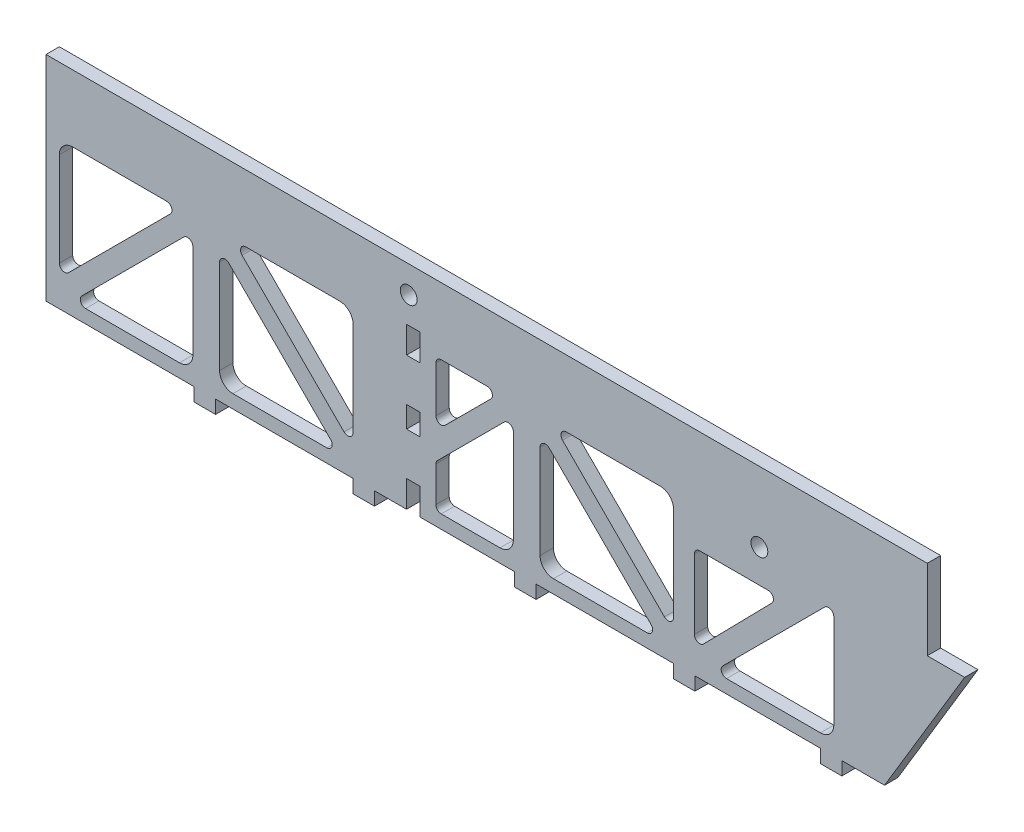
SolidWorks part; units mm, degrees
material "Pine"
ref_plane "Front Plane" through (0, 0, 0) normal (0, 0, 1) x (1, 0, 0)
ref_plane "Top Plane" through (0, 0, 0) normal (0, 1, 0) x (1, 0, 0)
ref_plane "Right Plane" through (0, 0, 0) normal (1, 0, 0) x (0, 0, -1)
sketch "Model" plane through (0, 0, 0) normal (0, 0, 1) x (1, 0, 0)
  line L0 (312.6855, 15.1239) -> (345.2281, 48.2988)
  line L1 (343.4149, 52.6175) -> (310.8722, 52.6175)
  line L2 (308.3322, 50.0775) -> (308.3322, 16.9026)
  line L8 (171.2321, 6.35) -> (215.9, 6.35)
  line L9 (217.9139, 59.1639) -> (169.4361, 10.6861)
  line L10 (222.25, 57.3679) -> (222.25, 12.7)
  line L11 (234.95, 57.3679) -> (234.95, 12.7)
  line L12 (239.2861, 59.1639) -> (287.7639, 10.6861)
  line L13 (241.3, 6.35) -> (285.9679, 6.35)
  line L14 (294.1139, 17.0361) -> (245.6361, 65.5139)
  line L15 (247.4321, 69.85) -> (292.1, 69.85)
  line L16 (298.45, 63.5) -> (298.45, 18.8321)
  line L17 (323.6321, 6.35) -> (368.3, 6.35)
  line L18 (370.3139, 59.1639) -> (321.8361, 10.6861)
  line L19 (374.65, 57.3679) -> (374.65, 12.7)
  line L20 (18.8321, 6.35) -> (63.5, 6.35)
  line L21 (17.0361, 10.6861) -> (65.5139, 59.1639)
  line L22 (69.85, 57.3679) -> (69.85, 12.7)
  line L23 (82.55, 57.3679) -> (82.55, 12.7)
  line L24 (86.8861, 59.1639) -> (135.3639, 10.6861)
  line L25 (88.9, 6.35) -> (133.5679, 6.35)
  line L26 (93.2361, 65.5139) -> (141.7139, 17.0361)
  line L27 (95.0321, 69.85) -> (139.7, 69.85)
  line L28 (146.05, 63.5) -> (146.05, 18.8321)
  line L29 (163.0861, 17.0361) -> (211.5639, 65.5139)
  line L30 (158.75, 63.5) -> (158.75, 18.8321)
  line L31 (165.1, 69.85) -> (209.7679, 69.85)
  line L35 (419.1, 87.376) -> (419.1, 71.374)
  line L36 (436.88, 87.376) -> (419.1, 87.376)
  line L37 (436.88, 87.376) -> (436.88, 95.25)
  line L38 (0, 95.25) -> (436.88, 95.25)
  line L39 (0, 0) -> (0, 95.25)
  line L40 (0, 0) -> (398.78, 0)
  line L41 (436.88, 63.5) -> (398.78, 0)
  line L42 (436.88, 63.5) -> (436.88, 71.374)
  line L43 (419.1, 71.374) -> (436.88, 71.374)
  line L44 (6.35, 63.5) -> (6.35, 18.8321)
  line L45 (12.7, 69.85) -> (57.3679, 69.85)
  line L46 (59.1639, 65.5139) -> (10.6861, 17.0361)
  arc A0 (215.9, 6.35) -> (222.25, 12.7) centre (215.9, 12.7) ccw
  arc A1 (169.4361, 10.6861) -> (171.2321, 6.35) centre (171.2321, 8.89) ccw
  arc A2 (222.25, 57.3679) -> (217.9139, 59.1639) centre (219.71, 57.3679) ccw
  arc A3 (239.2861, 59.1639) -> (234.95, 57.3679) centre (237.49, 57.3679) ccw
  arc A4 (285.9679, 6.35) -> (287.7639, 10.6861) centre (285.9679, 8.89) ccw
  arc A5 (234.95, 12.7) -> (241.3, 6.35) centre (241.3, 12.7) ccw
  arc A6 (247.4321, 69.85) -> (245.6361, 65.5139) centre (247.4321, 67.31) ccw
  arc A7 (298.45, 63.5) -> (292.1, 69.85) centre (292.1, 63.5) ccw
  arc A8 (294.1139, 17.0361) -> (298.45, 18.8321) centre (295.91, 18.8321) ccw
  arc A9 (321.8361, 10.6861) -> (323.6321, 6.35) centre (323.6321, 8.89) ccw
  arc A10 (374.65, 57.3679) -> (370.3139, 59.1639) centre (372.11, 57.3679) ccw
  arc A11 (368.3, 6.35) -> (374.65, 12.7) centre (368.3, 12.7) ccw
  arc A12 (63.5, 6.35) -> (69.85, 12.7) centre (63.5, 12.7) ccw
  arc A13 (17.0361, 10.6861) -> (18.8321, 6.35) centre (18.8321, 8.89) ccw
  arc A14 (69.85, 57.3679) -> (65.5139, 59.1639) centre (67.31, 57.3679) ccw
  arc A15 (86.8861, 59.1639) -> (82.55, 57.3679) centre (85.09, 57.3679) ccw
  arc A16 (133.5679, 6.35) -> (135.3639, 10.6861) centre (133.5679, 8.89) ccw
  arc A17 (82.55, 12.7) -> (88.9, 6.35) centre (88.9, 12.7) ccw
  arc A18 (95.0321, 69.85) -> (93.2361, 65.5139) centre (95.0321, 67.31) ccw
  arc A19 (146.05, 63.5) -> (139.7, 69.85) centre (139.7, 63.5) ccw
  arc A20 (141.7139, 17.0361) -> (146.05, 18.8321) centre (143.51, 18.8321) ccw
  arc A21 (158.75, 18.8321) -> (163.0861, 17.0361) centre (161.29, 18.8321) ccw
  arc A22 (165.1, 69.85) -> (158.75, 63.5) centre (165.1, 63.5) ccw
  arc A23 (211.5639, 65.5139) -> (209.7679, 69.85) centre (209.7679, 67.31) ccw
  arc A24 (345.2281, 48.2988) -> (343.4149, 52.6175) centre (343.4149, 50.0775) ccw
  arc A25 (310.8722, 52.6175) -> (308.3322, 50.0775) centre (310.8722, 50.0775) ccw
  arc A26 (312.6855, 15.1239) -> (308.3322, 16.9026) centre (310.8722, 16.9026) cw
  arc A27 (6.35, 18.8321) -> (10.6861, 17.0361) centre (8.89, 18.8321) ccw
  arc A28 (12.7, 69.85) -> (6.35, 63.5) centre (12.7, 63.5) ccw
  arc A29 (59.1639, 65.5139) -> (57.3679, 69.85) centre (57.3679, 67.31) ccw
  circle A30 centre (172.4917, 88.8013) radius 4
  circle A31 centre (339.2605, 68.3246) radius 4
  circle A32 centre (172.4917, 88.8013) radius 168.021 construction
  dimension "D2" = 6.4487
  dimension "D3" = 172.4917
  dimension "D4" = 8
  dimension "D5" = 20.4767
  dimension "D6" = 8
  dimension "D8" = 2.54
  dimension "D1" = 95.25
  dimension "D7" = 166.7688
extrude "Boss-Extrude2" add sketch "Model" along normal blind 6.35
sketch "Sketch1" plane through (0, 0, 6.35) normal (0, 0, 1) x (1, 0, 0)
  line L0 (69.85, 12.7) -> (69.85, 57.3679) construction
  line L1 (146.05, 95.25) -> (146.05, 0) construction
  line L2 (146.05, 18.8321) -> (146.05, 63.5) construction
  line L3 (0, 0) -> (398.78, 0) construction
  line L4 (222.25, 12.7) -> (222.25, 57.3679) construction
  line L6 (298.45, 18.8321) -> (298.45, 0) construction
  line L7 (146.05, 0) -> (156.21, 0)
  line L8 (70.485, 0) -> (80.645, 0)
  line L9 (70.485, 0) -> (70.485, -6.35)
  line L10 (70.485, -6.35) -> (80.645, -6.35)
  line L11 (80.645, 0) -> (80.645, -6.35)
  line L16 (222.885, 0) -> (233.045, 0)
  line L17 (222.885, 0) -> (222.885, -6.35)
  line L18 (222.885, -6.35) -> (233.045, -6.35)
  line L19 (233.045, 0) -> (233.045, -6.35)
  line L20 (146.05, 0) -> (146.05, -6.35)
  line L21 (146.05, -6.35) -> (156.21, -6.35)
  line L22 (156.21, 0) -> (156.21, -6.35)
  line L27 (298.45, 0) -> (308.61, 0)
  line L28 (298.45, 0) -> (298.45, -6.35)
  line L29 (298.45, -6.35) -> (308.61, -6.35)
  line L30 (308.61, 0) -> (308.61, -6.35)
  line L31 (368.3, 0) -> (378.46, 0)
  line L32 (368.3, 0) -> (368.3, -6.35)
  line L33 (368.3, -6.35) -> (378.46, -6.35)
  line L34 (378.46, 0) -> (378.46, -6.35)
  line L39 (0, 101.6) -> (436.88, 101.6)
  line L53 (0, 95.25) -> (0, 101.6)
  line L55 (436.88, 95.25) -> (436.88, 101.6)
  line L56 (436.88, 95.25) -> (0, 95.25) construction
  line L57 (0, 95.25) -> (436.88, 95.25)
  dimension "D1" = 10.16
  dimension "D2" = 6.35
  dimension "D3" = 10.16
  dimension "D4" = 6.35
  dimension "D5" = 10.16
  dimension "D6" = 10.16
  dimension "D7" = 10.16
  dimension "D8" = 20.32
  dimension "D9" = 0.635
  dimension "D10" = 0.635
  dimension "D13" = 6.35
extrude "Boss-Extrude3" add sketch "Sketch1" against normal up to surface (6.35 mm away) up to face at (321.5295, 39.2174, 0)
sketch "Sketch2" plane through (0, 0, 6.35) normal (0, 0, 1) x (1, 0, 0)
  line L0 (156.21, 0) -> (222.885, 0) construction
  line L1 (165.1, 79.7539) -> (185.42, 79.7539)
  line L2 (165.1, 79.7539) -> (165.1, 0)
  line L3 (165.1, 0) -> (185.42, 0)
  line L4 (185.42, 79.7539) -> (185.42, 0)
  line L5 (158.75, 63.5) -> (158.75, 18.8321) construction
  line L7 (171.45, 0) -> (177.8, 0)
  line L8 (171.45, 0) -> (171.45, 12.7)
  line L9 (171.45, 12.7) -> (177.8, 12.7)
  line L10 (177.8, 0) -> (177.8, 12.7)
  line L11 (171.45, 33.02) -> (177.8, 33.02)
  line L12 (171.45, 33.02) -> (171.45, 43.18)
  line L13 (171.45, 43.18) -> (177.8, 43.18)
  line L14 (177.8, 33.02) -> (177.8, 43.18)
  line L15 (171.45, 63.5) -> (177.8, 63.5)
  line L16 (171.45, 63.5) -> (171.45, 76.2)
  line L17 (171.45, 76.2) -> (177.8, 76.2)
  line L18 (177.8, 63.5) -> (177.8, 76.2)
  line L19 (146.05, -6.35) -> (156.21, -6.35) construction
  dimension "D1" = 6.35
  dimension "D2" = 20.32
  dimension "D3" = 6.35
  dimension "D4" = 6.35
  dimension "D5" = 6.35
  dimension "D6" = 12.7
  dimension "D7" = 20.32
  dimension "D8" = 20.32
  dimension "D9" = 10.16
  dimension "D10" = 12.7
extrude "Boss-Extrude4" add sketch "Sketch2" against normal up to surface (6.35 mm away) contours L10 L3 L4 L1 L2 L8 L9 L18 L15 L16 L17 L14 L11 L12 L13 region at (175.26, 78.9309, 6.35) up to face at (321.5295, 39.2174, 0)
extrude "Cut-Extrude1" cut sketch "Sketch2<3>" along direction (0, 0, 1) on the side against the normal up to surface (6.35 mm away) from surface contours L3 L10 L9 L8 | L15 L18 L17 L16 region at (174.625, 6.35, 6.35) region at (174.625, 69.85, 6.35) up to face at (174.625, 9.525, 0) starting at face at (174.625, 9.525, 6.35)
sketch "Sketch2<3>" plane through (0, 0, 6.35) normal (0, 0, 1) x (1, 0, 0) same geometry as "Sketch2"
sketch "Sketch3" plane through (0, 0, 6.35) normal (0, 0, 1) x (1, 0, 0)
  line L1 (154.8502, 72.8404) -> (168.7325, 72.8404)
  line L2 (154.8502, 72.8404) -> (154.8502, 13.7288)
  line L3 (154.8502, 13.7288) -> (168.7325, 13.7288)
  line L4 (168.7325, 72.8404) -> (168.7325, 13.7288)
extrude "Boss-Extrude5" add sketch "Sketch3" against normal up to surface (6.35 mm away) up to face at (174.625, 69.85, 0)
sketch "Sketch4" plane through (0, 0, 6.35) normal (0, 0, 1) x (1, 0, 0)
  line L0 (209.7679, 69.85) -> (185.42, 69.85) construction
  line L1 (185.42, 39.37) -> (211.5639, 65.5139) construction
  line L2 (185.42, 69.85) -> (185.42, 39.37) construction
  line L3 (185.42, 6.35) -> (215.9, 6.35) construction
  line L4 (185.42, 26.67) -> (185.42, 6.35) construction
  line L5 (209.7679, 69.85) -> (187.96, 69.85)
  line L6 (189.7561, 43.7061) -> (211.5639, 65.5139)
  line L7 (185.42, 67.31) -> (185.42, 45.5021)
  line L8 (187.96, 6.35) -> (215.9, 6.35)
  line L9 (185.42, 25.6179) -> (185.42, 8.89)
  line L10 (185.42, 45.5021) -> (185.42, 39.37)
  line L11 (185.42, 39.37) -> (189.7561, 43.7061)
  line L12 (185.42, 67.31) -> (185.42, 69.85)
  line L13 (185.42, 69.85) -> (187.96, 69.85)
  line L14 (185.42, 8.89) -> (185.42, 6.35)
  line L15 (185.42, 6.35) -> (187.96, 6.35)
  line L16 (185.42, 8.89) -> (185.42, 6.35)
  line L17 (217.9139, 59.1639) -> (185.42, 26.67) construction
  line L18 (217.9139, 59.1639) -> (186.1639, 27.4139)
  line L19 (185.42, 25.6179) -> (185.42, 26.67)
  line L20 (185.42, 26.67) -> (186.1639, 27.4139)
  arc A0 (187.96, 69.85) -> (185.42, 67.31) centre (187.96, 67.31) ccw
  arc A1 (189.7561, 43.7061) -> (185.42, 45.5021) centre (187.96, 45.5021) cw
  arc A2 (187.96, 6.35) -> (185.42, 8.89) centre (187.96, 8.89) cw
  arc A3 (185.42, 25.6179) -> (186.1639, 27.4139) centre (187.96, 25.6179) cw
  dimension "D1" = 2.54
  dimension "D2" = 2.54
extrude "Boss-Extrude6" add sketch "Sketch4" against normal up to surface (6.35 mm away) contours L11 A1 L10 | A0 L13 L12 | L15 A2 L14 | L19 A3 L20 region at (186.5486, 42.0946, 6.35) region at (185.9874, 69.2826, 6.35) region at (185.9874, 6.9174, 6.35) region at (185.5728, 26.6067, 6.35) up to face at (174.625, 69.85, 0)
sketch "Sketch5" plane through (0, 0, 6.35) normal (0, 0, 1) x (1, 0, 0)
  line L1 (436.88, 101.6) -> (419.1, 101.6)
  line L2 (436.88, 101.6) -> (436.88, 63.5)
  line L3 (436.88, 63.5) -> (419.1, 63.5)
  line L4 (419.1, 101.6) -> (419.1, 63.5)
  dimension "D1" = 17.78
  dimension "D2" = 38.1
extrude "Cut-Extrude2" cut sketch "Sketch5" against normal up to surface (6.35 mm away) up to face at (203.061, 25.4419, 0)
